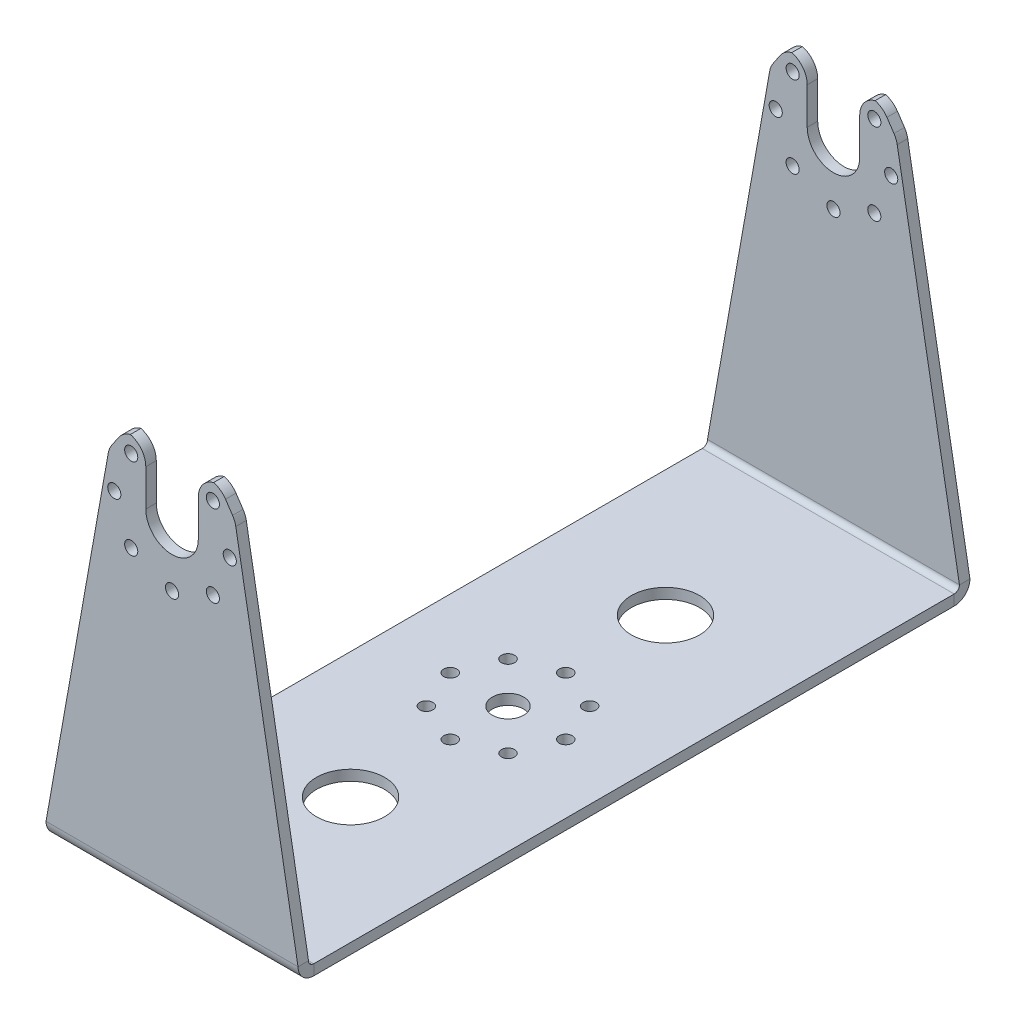
SolidWorks part; units mm, degrees
note: The reader was unsure of these and kept them because the rebuilt part matched: thickness of "Flange-base1", "Aresta-Flange1", "Chapa metálica1", "Chapa metálica2", "Chapa metálica4", "Chapa metálica5", "Chapa metálica6"; flange length of "Aresta-Flange1".
material "5052-H32"
ref_plane "Plano frontal" through (0, 0, 0) normal (0, 0, 1) x (1, 0, 0)
ref_plane "Plano superior" through (0, 0, 0) normal (0, 1, 0) x (1, 0, 0)
ref_plane "Plano direito" through (0, 0, 0) normal (1, 0, 0) x (0, 0, -1)
sketch "Esboço1" plane through (0, 0, 0) normal (0, 1, 0) x (1, 0, 0)
  line L1 (24, -62) -> (-24, -62)
  line L2 (24, -62) -> (24, 62)
  line L3 (24, 62) -> (-24, 62)
  line L4 (-24, -62) -> (-24, 62)
  line L5 (24, -62) -> (-24, 62) construction
  line L6 (24, 62) -> (-24, -62) construction
  point P0 (0, 0)
  dimension "D1" = 48
  dimension "D2" = 124
base flange "Flange-base1" sketch "Esboço1" thickness 2 reverse thickness direction no parameters "D1"=10
edge flange "Aresta-Flange1" sketch "Esboço8" flange profiles "Esboço8", "Esboço13" flange angle 90 flange length 75 flange position material outside bend radius 1 thickness 2 relief rectangular parameters "D6"=10, "D8"=1
sketch "Esboço8" plane through (0, 0, 62) normal (0, 0, 1) x (1, 0, 0)
  line L2 (-24, 0) -> (-24, 73)
  line L3 (-24, 73) -> (24, 73)
  line L4 (24, 73) -> (24, 0)
  line L5 (-24, 0) -> (24, 0) construction
  line L6 (-24, 0) -> (24, 0)
sketch "Esboço13" plane through (0, 0, -62) normal (0, 0, -1) x (-1, 0, 0)
  line L0 (-24, 0) -> (24, 0) construction
  line L1 (-24, 0) -> (24, 0)
  line L2 (-24, 0) -> (-24, 73)
  line L3 (-24, 73) -> (24, 73)
  line L4 (24, 73) -> (24, 0)
bend "DobradeAresta1" bend radius 1 bend angle 90 parameters "D5"=1
bend "DobradeAresta3" bend radius 1 bend angle 90 parameters "D5"=3
sketch "Esboço14" plane through (0, 0, 64) normal (0, 0, 1) x (1, 0, 0)
  line L0 (0, 0) -> (0, 73) construction
  line L1 (24, 73) -> (-24, 73) construction
  line L2 (-5, 62) -> (-5, 73)
  line L3 (-5, 73) -> (5, 73)
  line L4 (5, 73) -> (5, 62)
  line L5 (-24, 1) -> (-12, 68.5282)
  line L6 (-24, 73) -> (-9, 73)
  line L7 (-24, 73) -> (-24, 1)
  line L8 (-7.7782, 68.5282) -> (-17.9746, 68.5282) construction
  line L9 (7.7782, 68.5282) -> (17.9746, 68.5282) construction
  line L10 (24, 73) -> (9, 73)
  line L11 (-12, 68.5282) -> (-9, 73)
  line L12 (12, 68.5282) -> (9, 73)
  line L13 (24, 1) -> (12, 68.5282)
  line L14 (24, 73) -> (24, 1)
  circle A0 centre (0, 62) radius 1.548 construction
  circle A1 centre (-11, 62) radius 1.25
  circle A2 centre (-7.7782, 69.7782) radius 1.25
  circle A4 centre (7.7782, 69.7782) radius 1.25
  circle A5 centre (11, 62) radius 1.25
  circle A6 centre (7.7782, 54.2218) radius 1.25
  circle A7 centre (0, 51) radius 1.25
  circle A8 centre (-7.7782, 54.2218) radius 1.25
  arc A9 (-5, 62) -> (5, 62) centre (0, 62) ccw
  circle A10 centre (0, 73) radius 1.25 [skipped]
  point P26 (0, 62)
  dimension "D1" = 2.5
  dimension "D2" = 11
  dimension "D5" = 10
  dimension "D4" = 11
  dimension "D6" = 12
  dimension "D7" = 4
  dimension "D3" = 8
extrude "Corte-extrusão1" cut sketch "Esboço14" against normal up to surface (128 mm away) normal cut yes up to face at (0, 37, -64)
sketch "Esboço15" plane through (0, 0, 0) normal (0, 1, 0) x (1, 0, 0)
  circle A0 centre (0, -30) radius 6.5
  circle A1 centre (0, 30) radius 6.5
  dimension "D1" = 13
  dimension "D3" = 30
  dimension "D2" = 30
extrude "Corte-extrusão2" cut sketch "Esboço15" against normal up to surface (2 mm away) normal cut yes up to face at (0, -2, 0)
fillet "Filete1" radius 4 12 edges at (-12, 68.5282, -63) (-9, 73, -63) (-5, 73, -63) (5, 73, -63) (12, 68.5282, -63) (9, 73, -63) (12, 68.5282, 63) (9, 73, 63) (5, 73, 63) (-9, 73, 63) (-12, 68.5282, 63) (-5, 73, 63)
sketch "Esboço16" plane through (0, -2, 0) normal (0, -1, 0) x (1, 0, 0)
  circle A0 centre (0, 0) radius 3
  circle A1 centre (0, 11) radius 1.25
  circle A2 centre (7.7782, 7.7782) radius 1.25
  circle A3 centre (11, 0) radius 1.25
  circle A4 centre (7.7782, -7.7782) radius 1.25
  circle A5 centre (0, -11) radius 1.25
  circle A6 centre (-7.7782, -7.7782) radius 1.25
  circle A7 centre (-11, 0) radius 1.25
  circle A8 centre (-7.7782, 7.7782) radius 1.25
  point P21 (0, 0)
  dimension "D1" = 6
  dimension "D2" = 11
  dimension "D3" = 2.5
  dimension "D5" = 11
  dimension "D4" = 8
extrude "Corte-extrusão3" cut sketch "Esboço16" against normal up to surface (2 mm away) normal cut yes up to face at (0, 0, -23.5)
sketch "Curva-Linhas1" [suppressed] plane through (0, 0, 0) normal (0, 1, 0) x (1, 0, 0)
sketch "Caixa delimitadora1" [suppressed] plane through (0, 0, 0) normal (0, 1, 0) x (1, 0, 0)
sheet metal parameters "Chapa metálica1" thickness 2 parameters "D1"=10
flat pattern "Padrão-Plano1" [suppressed]
sketch "Curva-Linhas2" plane through (0, 0, 0) normal (0, 1, 0) x (1, 0, 0)
sketch3d "Caixa delimitadora2" [suppressed]
  line L0 (24, 62, 0) -> (24, -62, 0) construction
  line L1 (-24, 62, 0) -> (-24, -62, 0) construction
  line L2 (24, 62, 0) -> (-24, 62, 0) construction
  line L3 (24, -62, 0) -> (-24, -62, 0) construction
sheet metal parameters "Chapa metálica2" thickness 2 parameters "D1"=10, "D7"=4
flat pattern "Padrão-Plano1"
sketch "Curva-Linhas2" plane through (0, 0, 0) normal (0, 1, 0) x (1, 0, 0)
  line L0 (-24, -62.7124) -> (24, -62.7124) construction
  line L1 (-24, -62.7124) -> (24, -62.7124) construction
  line L2 (24, 62.7124) -> (-24, 62.7124) construction
  line L3 (24, 62.7124) -> (-24, 62.7124) construction
sketch3d "Caixa delimitadora2" [suppressed]
  line L0 (-24, 108.4248, 0) -> (-24, -108.4248, 0) construction
  line L1 (24, 108.4248, 0) -> (24, -108.4248, 0) construction
  line L2 (-24, 108.4248, 0) -> (24, 108.4248, 0) construction
  line L3 (-24, -108.4248, 0) -> (24, -108.4248, 0) construction
bend of the flat pattern "Planificar-<DobradeAresta1>1"
bend of the flat pattern "Planificar-<DobradeAresta3>1"
sheet metal parameters "Chapa metálica4" thickness 2 parameters "D1"=10, "D7"=4
flat pattern "Padrão-Plano1"
sketch "Curva-Linhas2" plane through (0, 0, 0) normal (0, 1, 0) x (1, 0, 0)
  line L0 (-24, -62.7124) -> (24, -62.7124) construction
  line L1 (-24, -62.7124) -> (24, -62.7124) construction
  line L2 (24, 62.7124) -> (-24, 62.7124) construction
  line L3 (24, 62.7124) -> (-24, 62.7124) construction
sketch3d "Caixa delimitadora2" [suppressed]
  line L0 (-24, 108.4247, 0) -> (-24, -108.4247, 0) construction
  line L1 (24, 108.4247, 0) -> (24, -108.4247, 0) construction
  line L2 (-24, 108.4247, 0) -> (24, 108.4247, 0) construction
  line L3 (-24, -108.4247, 0) -> (24, -108.4247, 0) construction
bend of the flat pattern "Planificar-<DobradeAresta1>1"
bend of the flat pattern "Planificar-<DobradeAresta3>1"
sheet metal parameters "Chapa metálica5" thickness 2 parameters "D1"=10, "D7"=4
flat pattern "Padrão-Plano1"
sketch "Curva-Linhas2" plane through (0, 0, 0) normal (0, 1, 0) x (1, 0, 0)
  line L0 (-24, -62.5708) -> (24, -62.5708) construction
  line L1 (-24, -62.5708) -> (24, -62.5708) construction
  line L2 (24, 62.5708) -> (-24, 62.5708) construction
  line L3 (24, 62.5708) -> (-24, 62.5708) construction
sketch3d "Caixa delimitadora2" [suppressed]
  line L0 (-24, 135.9968, 0) -> (-24, -135.9968, 0) construction
  line L1 (24, 135.9968, 0) -> (24, -135.9968, 0) construction
  line L2 (-24, 135.9968, 0) -> (24, 135.9968, 0) construction
  line L3 (-24, -135.9968, 0) -> (24, -135.9968, 0) construction
bend of the flat pattern "Planificar-<DobradeAresta1>1"
bend of the flat pattern "Planificar-<DobradeAresta3>1"
sheet metal parameters "Chapa metálica6" thickness 2 parameters "D1"=10, "D7"=4
flat pattern "Padrão-Plano1"
sketch "Curva-Linhas2" plane through (0, 0, 0) normal (0, 1, 0) x (1, 0, 0)
  line L0 (-24, -62.5708) -> (24, -62.5708) construction
  line L1 (-24, -62.5708) -> (24, -62.5708) construction
  line L2 (24, 62.5708) -> (-24, 62.5708) construction
  line L3 (24, 62.5708) -> (-24, 62.5708) construction
sketch3d "Caixa delimitadora2" [suppressed]
  line L0 (-24, 135.9968, 0) -> (-24, -135.9968, 0) construction
  line L1 (24, 135.9968, 0) -> (24, -135.9968, 0) construction
  line L2 (-24, 135.9968, 0) -> (24, 135.9968, 0) construction
  line L3 (-24, -135.9968, 0) -> (24, -135.9968, 0) construction
bend of the flat pattern "Planificar-<DobradeAresta1>1"
bend of the flat pattern "Planificar-<DobradeAresta3>1"
